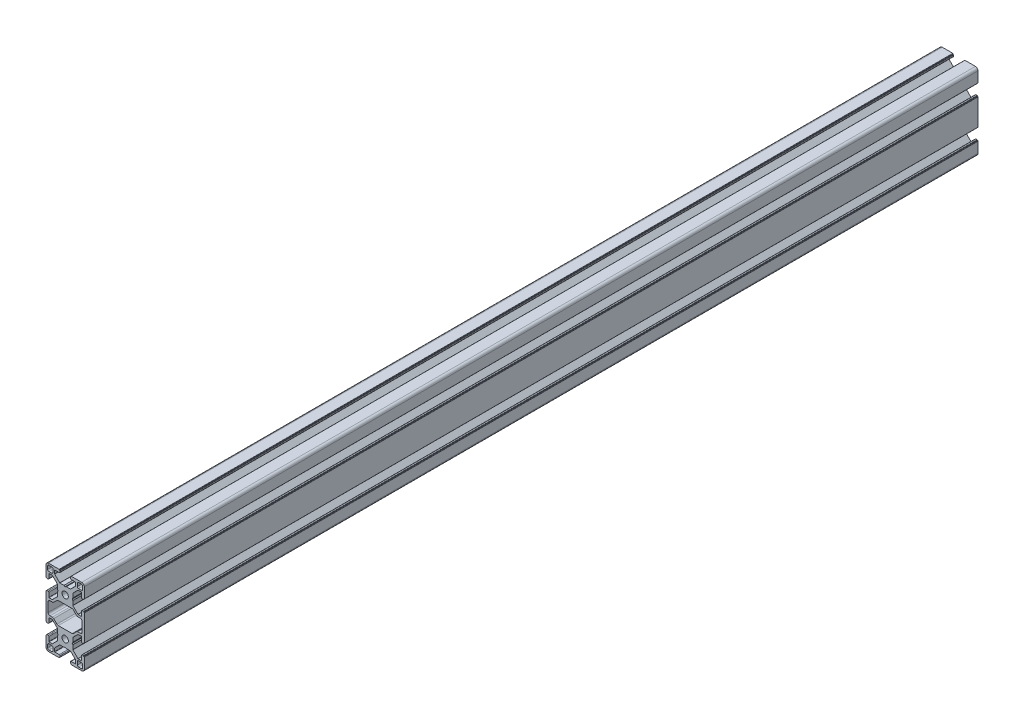
SolidWorks part; units mm, degrees
material "1060 Alloy"
ref_plane "Front" through (0, 0, 0) normal (0, 0, 1) x (1, 0, 0)
ref_plane "Top" through (0, 0, 0) normal (0, 1, 0) x (1, 0, 0)
ref_plane "Right" through (0, 0, 0) normal (1, 0, 0) x (0, 0, -1)
ref_plane "Plane1" through (0, 0, 25) normal (0, 0, 1) x (1, 0, 0)
sketch "Sketch1" plane through (0, 0, 25) normal (0, 0, 1) x (1, 0, 0)
  line L0 (-9.5, 12.7) -> (-9.5, 10.5)
  line L1 (-10.5, 9.5) -> (-12.7, 9.5)
  line L2 (-13.7, 10.5) -> (-13.7, 12.7)
  line L3 (-12.7, 13.7) -> (-10.5, 13.7)
  line L4 (12.7, 9.5) -> (10.5, 9.5)
  line L5 (9.5, 10.5) -> (9.5, 12.7)
  line L6 (10.5, 13.7) -> (12.7, 13.7)
  line L7 (13.7, 12.7) -> (13.7, 10.5)
  line L8 (-12.7, -39.5) -> (-10.5, -39.5)
  line L9 (-9.5, -40.5) -> (-9.5, -42.7)
  line L10 (-10.5, -43.7) -> (-12.7, -43.7)
  line L11 (-13.7, -42.7) -> (-13.7, -40.5)
  line L12 (9.5, -42.7) -> (9.5, -40.5)
  line L13 (10.5, -39.5) -> (12.7, -39.5)
  line L14 (13.7, -40.5) -> (13.7, -42.7)
  line L15 (12.7, -43.7) -> (10.5, -43.7)
  line L16 (0, 0) -> (0, -30) construction
  line L32 (8.9272, -20.5393) -> (6.4104, -23.0562)
  line L33 (5.3497, -23.4955) -> (-5.3497, -23.4955)
  line L34 (-6.4104, -23.0562) -> (-8.9272, -20.5393)
  line L35 (-9.9879, -20.1) -> (-11.85, -20.1)
  line L36 (-13.35, -18.6) -> (-13.35, -11.4)
  line L37 (-11.85, -9.9) -> (-9.9879, -9.9)
  line L38 (-8.9272, -9.4607) -> (-6.4104, -6.9438)
  line L39 (-5.3497, -6.5045) -> (5.3497, -6.5045)
  line L40 (6.4104, -6.9438) -> (8.9272, -9.4607)
  line L41 (9.9879, -9.9) -> (11.85, -9.9)
  line L42 (13.35, -11.4) -> (13.35, -18.6)
  line L43 (11.85, -20.1) -> (9.9879, -20.1)
  line L44 (13.4, -25.95) -> (14.3, -25.95)
  line L45 (14.5, -25.75) -> (14.5, -25.65)
  line L46 (14.7, -25.45) -> (14.8, -25.45)
  line L47 (15, -25.25) -> (15, -4.75)
  line L48 (14.8, -4.55) -> (14.7, -4.55)
  line L49 (14.5, -4.35) -> (14.5, -4.25)
  line L50 (14.3, -4.05) -> (13.4, -4.05)
  line L51 (12.8, -4.65) -> (12.8, -8.05)
  line L52 (12.6, -8.25) -> (10.1328, -8.25)
  line L53 (9.9914, -8.1914) -> (6.063, -4.263)
  line L54 (6.0045, -4.1216) -> (6.0045, -0.9)
  line L55 (6.0045, -0.9) -> (5.5426, -0.1)
  line L56 (5.5426, 0.1) -> (6.0045, 0.9)
  line L57 (6.0045, 0.9) -> (6.0045, 4.1216)
  line L58 (6.063, 4.263) -> (9.9914, 8.1914)
  line L59 (10.1328, 8.25) -> (12.6, 8.25)
  line L60 (12.8, 8.05) -> (12.8, 4.65)
  line L61 (13.4, 4.05) -> (14.3, 4.05)
  line L62 (14.5, 4.25) -> (14.5, 4.35)
  line L63 (14.7, 4.55) -> (14.8, 4.55)
  line L64 (15, 4.75) -> (15, 13)
  line L65 (13, 15) -> (4.75, 15)
  line L66 (4.55, 14.8) -> (4.55, 14.7)
  line L67 (4.35, 14.5) -> (4.25, 14.5)
  line L68 (4.05, 14.3) -> (4.05, 13.4)
  line L69 (4.65, 12.8) -> (8.05, 12.8)
  line L70 (8.25, 12.6) -> (8.25, 10.1328)
  line L71 (8.1914, 9.9914) -> (4.2586, 6.0586)
  line L72 (4.1172, 6) -> (0.9, 6)
  line L73 (0.9, 6) -> (0.1019, 5.5392)
  line L74 (-0.1019, 5.5392) -> (-0.9, 6)
  line L75 (-0.9, 6) -> (-4.1172, 6)
  line L76 (-4.2586, 6.0586) -> (-8.1914, 9.9914)
  line L77 (-8.25, 10.1328) -> (-8.25, 12.6)
  line L78 (-8.05, 12.8) -> (-4.65, 12.8)
  line L79 (-4.05, 13.4) -> (-4.05, 14.3)
  line L80 (-4.25, 14.5) -> (-4.35, 14.5)
  line L81 (-4.55, 14.7) -> (-4.55, 14.8)
  line L82 (-4.75, 15) -> (-13, 15)
  line L83 (-15, 13) -> (-15, 4.75)
  line L84 (-14.8, 4.55) -> (-14.7, 4.55)
  line L85 (-14.5, 4.35) -> (-14.5, 4.25)
  line L86 (-14.3, 4.05) -> (-13.4, 4.05)
  line L87 (-12.8, 4.65) -> (-12.8, 8.05)
  line L88 (-12.6, 8.25) -> (-10.1328, 8.25)
  line L89 (-9.9914, 8.1914) -> (-6.063, 4.263)
  line L90 (-6.0045, 4.1216) -> (-6.0045, 0.9)
  line L91 (-6.0045, 0.9) -> (-5.5426, 0.1)
  line L92 (-5.5426, -0.1) -> (-6.0045, -0.9)
  line L93 (-6.0045, -0.9) -> (-6.0045, -4.1216)
  line L94 (-6.063, -4.263) -> (-9.9914, -8.1914)
  line L95 (-10.1328, -8.25) -> (-12.6, -8.25)
  line L96 (-12.8, -8.05) -> (-12.8, -4.65)
  line L97 (-13.4, -4.05) -> (-14.3, -4.05)
  line L98 (-14.5, -4.25) -> (-14.5, -4.35)
  line L99 (-14.7, -4.55) -> (-14.8, -4.55)
  line L100 (-15, -4.75) -> (-15, -25.25)
  line L101 (-14.8, -25.45) -> (-14.7, -25.45)
  line L102 (-14.5, -25.65) -> (-14.5, -25.75)
  line L103 (-14.3, -25.95) -> (-13.4, -25.95)
  line L104 (-12.8, -25.35) -> (-12.8, -21.95)
  line L105 (-12.6, -21.75) -> (-10.1328, -21.75)
  line L106 (-9.9914, -21.8086) -> (-6.063, -25.737)
  line L107 (-6.0045, -25.8784) -> (-6.0045, -29.1)
  line L108 (-6.0045, -29.1) -> (-5.5426, -29.9)
  line L109 (-5.5426, -30.1) -> (-6.0045, -30.9)
  line L110 (-6.0045, -30.9) -> (-6.0045, -34.1216)
  line L111 (-6.063, -34.263) -> (-9.9914, -38.1914)
  line L112 (-10.1328, -38.25) -> (-12.6, -38.25)
  line L113 (-12.8, -38.05) -> (-12.8, -34.65)
  line L114 (-13.4, -34.05) -> (-14.3, -34.05)
  line L115 (-14.5, -34.25) -> (-14.5, -34.35)
  line L116 (-14.7, -34.55) -> (-14.8, -34.55)
  line L117 (-15, -34.75) -> (-15, -43)
  line L118 (-13, -45) -> (-4.75, -45)
  line L119 (-4.55, -44.8) -> (-4.55, -44.7)
  line L120 (-4.35, -44.5) -> (-4.25, -44.5)
  line L121 (-4.05, -44.3) -> (-4.05, -43.4)
  line L122 (-4.65, -42.8) -> (-8.05, -42.8)
  line L123 (-8.25, -42.6) -> (-8.25, -40.1328)
  line L124 (-8.1914, -39.9914) -> (-4.2586, -36.0586)
  line L125 (-4.1172, -36) -> (-0.9, -36)
  line L126 (-0.9, -36) -> (-0.1019, -35.5392)
  line L127 (0.1019, -35.5392) -> (0.9, -36)
  line L128 (0.9, -36) -> (4.1172, -36)
  line L129 (4.2586, -36.0586) -> (8.1914, -39.9914)
  line L130 (8.25, -40.1328) -> (8.25, -42.6)
  line L131 (8.05, -42.8) -> (4.65, -42.8)
  line L132 (4.05, -43.4) -> (4.05, -44.3)
  line L133 (4.25, -44.5) -> (4.35, -44.5)
  line L134 (4.55, -44.7) -> (4.55, -44.8)
  line L135 (4.75, -45) -> (13, -45)
  line L136 (15, -43) -> (15, -34.75)
  line L137 (14.8, -34.55) -> (14.7, -34.55)
  line L138 (14.5, -34.35) -> (14.5, -34.25)
  line L139 (14.3, -34.05) -> (13.4, -34.05)
  line L140 (12.8, -34.65) -> (12.8, -38.05)
  line L141 (12.6, -38.25) -> (10.1328, -38.25)
  line L142 (9.9914, -38.1914) -> (6.063, -34.263)
  line L143 (6.0045, -34.1216) -> (6.0045, -30.9)
  line L144 (6.0045, -30.9) -> (5.5426, -30.1)
  line L145 (5.5426, -29.9) -> (6.0045, -29.1)
  line L146 (6.0045, -29.1) -> (6.0045, -25.8784)
  line L147 (6.063, -25.737) -> (9.9914, -21.8086)
  line L148 (10.1328, -21.75) -> (12.6, -21.75)
  line L149 (12.8, -21.95) -> (12.8, -25.35)
  arc A0 (-9.5, 10.5) -> (-10.5, 9.5) centre (-10.5, 10.5) cw
  arc A1 (-12.7, 9.5) -> (-13.7, 10.5) centre (-12.7, 10.5) cw
  arc A2 (-13.7, 12.7) -> (-12.7, 13.7) centre (-12.7, 12.7) cw
  arc A3 (-10.5, 13.7) -> (-9.5, 12.7) centre (-10.5, 12.7) cw
  arc A4 (10.5, 9.5) -> (9.5, 10.5) centre (10.5, 10.5) cw
  arc A5 (9.5, 12.7) -> (10.5, 13.7) centre (10.5, 12.7) cw
  arc A6 (12.7, 13.7) -> (13.7, 12.7) centre (12.7, 12.7) cw
  arc A7 (13.7, 10.5) -> (12.7, 9.5) centre (12.7, 10.5) cw
  arc A8 (-10.5, -39.5) -> (-9.5, -40.5) centre (-10.5, -40.5) cw
  arc A9 (-9.5, -42.7) -> (-10.5, -43.7) centre (-10.5, -42.7) cw
  arc A10 (-12.7, -43.7) -> (-13.7, -42.7) centre (-12.7, -42.7) cw
  arc A11 (-13.7, -40.5) -> (-12.7, -39.5) centre (-12.7, -40.5) cw
  arc A12 (9.5, -40.5) -> (10.5, -39.5) centre (10.5, -40.5) cw
  arc A13 (12.7, -39.5) -> (13.7, -40.5) centre (12.7, -40.5) cw
  arc A14 (13.7, -42.7) -> (12.7, -43.7) centre (12.7, -42.7) cw
  arc A15 (10.5, -43.7) -> (9.5, -42.7) centre (10.5, -42.7) cw
  circle A16 centre (0, 0) radius 2.45
  circle A17 centre (0, -30) radius 2.45
  arc A32 (6.4104, -23.0562) -> (5.3497, -23.4955) centre (5.3497, -21.9955) cw
  arc A33 (-5.3497, -23.4955) -> (-6.4104, -23.0562) centre (-5.3497, -21.9955) cw
  arc A34 (-8.9272, -20.5393) -> (-9.9879, -20.1) centre (-9.9879, -21.6) ccw
  arc A35 (-11.85, -20.1) -> (-13.35, -18.6) centre (-11.85, -18.6) cw
  arc A36 (-13.35, -11.4) -> (-11.85, -9.9) centre (-11.85, -11.4) cw
  arc A37 (-9.9879, -9.9) -> (-8.9272, -9.4607) centre (-9.9879, -8.4) ccw
  arc A38 (-6.4104, -6.9438) -> (-5.3497, -6.5045) centre (-5.3497, -8.0045) cw
  arc A39 (5.3497, -6.5045) -> (6.4104, -6.9438) centre (5.3497, -8.0045) cw
  arc A40 (8.9272, -9.4607) -> (9.9879, -9.9) centre (9.9879, -8.4) ccw
  arc A41 (11.85, -9.9) -> (13.35, -11.4) centre (11.85, -11.4) cw
  arc A42 (13.35, -18.6) -> (11.85, -20.1) centre (11.85, -18.6) cw
  arc A43 (9.9879, -20.1) -> (8.9272, -20.5393) centre (9.9879, -21.6) ccw
  arc A44 (12.8, -25.35) -> (13.4, -25.95) centre (13.4, -25.35) ccw
  arc A45 (14.3, -25.95) -> (14.5, -25.75) centre (14.3, -25.75) ccw
  arc A46 (14.5, -25.65) -> (14.7, -25.45) centre (14.7, -25.65) cw
  arc A47 (14.8, -25.45) -> (15, -25.25) centre (14.8, -25.25) ccw
  arc A48 (15, -4.75) -> (14.8, -4.55) centre (14.8, -4.75) ccw
  arc A49 (14.7, -4.55) -> (14.5, -4.35) centre (14.7, -4.35) cw
  arc A50 (14.5, -4.25) -> (14.3, -4.05) centre (14.3, -4.25) ccw
  arc A51 (13.4, -4.05) -> (12.8, -4.65) centre (13.4, -4.65) ccw
  arc A52 (12.8, -8.05) -> (12.6, -8.25) centre (12.6, -8.05) cw
  arc A53 (10.1328, -8.25) -> (9.9914, -8.1914) centre (10.1328, -8.05) cw
  arc A54 (6.063, -4.263) -> (6.0045, -4.1216) centre (6.2045, -4.1216) cw
  arc A55 (5.5426, -0.1) -> (5.5426, 0.1) centre (5.7158, 0) cw
  arc A56 (6.0045, 4.1216) -> (6.063, 4.263) centre (6.2045, 4.1216) cw
  arc A57 (9.9914, 8.1914) -> (10.1328, 8.25) centre (10.1328, 8.05) cw
  arc A58 (12.6, 8.25) -> (12.8, 8.05) centre (12.6, 8.05) cw
  arc A59 (12.8, 4.65) -> (13.4, 4.05) centre (13.4, 4.65) ccw
  arc A60 (14.3, 4.05) -> (14.5, 4.25) centre (14.3, 4.25) ccw
  arc A61 (14.5, 4.35) -> (14.7, 4.55) centre (14.7, 4.35) cw
  arc A62 (14.8, 4.55) -> (15, 4.75) centre (14.8, 4.75) ccw
  arc A63 (15, 13) -> (13, 15) centre (13, 13) ccw
  arc A64 (4.75, 15) -> (4.55, 14.8) centre (4.75, 14.8) ccw
  arc A65 (4.55, 14.7) -> (4.35, 14.5) centre (4.35, 14.7) cw
  arc A66 (4.25, 14.5) -> (4.05, 14.3) centre (4.25, 14.3) ccw
  arc A67 (4.05, 13.4) -> (4.65, 12.8) centre (4.65, 13.4) ccw
  arc A68 (8.05, 12.8) -> (8.25, 12.6) centre (8.05, 12.6) cw
  arc A69 (8.25, 10.1328) -> (8.1914, 9.9914) centre (8.05, 10.1328) cw
  arc A70 (4.2586, 6.0586) -> (4.1172, 6) centre (4.1172, 6.2) cw
  arc A71 (0.1019, 5.5392) -> (-0.1019, 5.5392) centre (0, 5.7158) cw
  arc A72 (-4.1172, 6) -> (-4.2586, 6.0586) centre (-4.1172, 6.2) cw
  arc A73 (-8.1914, 9.9914) -> (-8.25, 10.1328) centre (-8.05, 10.1328) cw
  arc A74 (-8.25, 12.6) -> (-8.05, 12.8) centre (-8.05, 12.6) cw
  arc A75 (-4.65, 12.8) -> (-4.05, 13.4) centre (-4.65, 13.4) ccw
  arc A76 (-4.05, 14.3) -> (-4.25, 14.5) centre (-4.25, 14.3) ccw
  arc A77 (-4.35, 14.5) -> (-4.55, 14.7) centre (-4.35, 14.7) cw
  arc A78 (-4.55, 14.8) -> (-4.75, 15) centre (-4.75, 14.8) ccw
  arc A79 (-13, 15) -> (-15, 13) centre (-13, 13) ccw
  arc A80 (-15, 4.75) -> (-14.8, 4.55) centre (-14.8, 4.75) ccw
  arc A81 (-14.7, 4.55) -> (-14.5, 4.35) centre (-14.7, 4.35) cw
  arc A82 (-14.5, 4.25) -> (-14.3, 4.05) centre (-14.3, 4.25) ccw
  arc A83 (-13.4, 4.05) -> (-12.8, 4.65) centre (-13.4, 4.65) ccw
  arc A84 (-12.8, 8.05) -> (-12.6, 8.25) centre (-12.6, 8.05) cw
  arc A85 (-10.1328, 8.25) -> (-9.9914, 8.1914) centre (-10.1328, 8.05) cw
  arc A86 (-6.063, 4.263) -> (-6.0045, 4.1216) centre (-6.2045, 4.1216) cw
  arc A87 (-5.5426, 0.1) -> (-5.5426, -0.1) centre (-5.7158, 0) cw
  arc A88 (-6.0045, -4.1216) -> (-6.063, -4.263) centre (-6.2045, -4.1216) cw
  arc A89 (-9.9914, -8.1914) -> (-10.1328, -8.25) centre (-10.1328, -8.05) cw
  arc A90 (-12.6, -8.25) -> (-12.8, -8.05) centre (-12.6, -8.05) cw
  arc A91 (-12.8, -4.65) -> (-13.4, -4.05) centre (-13.4, -4.65) ccw
  arc A92 (-14.3, -4.05) -> (-14.5, -4.25) centre (-14.3, -4.25) ccw
  arc A93 (-14.5, -4.35) -> (-14.7, -4.55) centre (-14.7, -4.35) cw
  arc A94 (-14.8, -4.55) -> (-15, -4.75) centre (-14.8, -4.75) ccw
  arc A95 (-15, -25.25) -> (-14.8, -25.45) centre (-14.8, -25.25) ccw
  arc A96 (-14.7, -25.45) -> (-14.5, -25.65) centre (-14.7, -25.65) cw
  arc A97 (-14.5, -25.75) -> (-14.3, -25.95) centre (-14.3, -25.75) ccw
  arc A98 (-13.4, -25.95) -> (-12.8, -25.35) centre (-13.4, -25.35) ccw
  arc A99 (-12.8, -21.95) -> (-12.6, -21.75) centre (-12.6, -21.95) cw
  arc A100 (-10.1328, -21.75) -> (-9.9914, -21.8086) centre (-10.1328, -21.95) cw
  arc A101 (-6.063, -25.737) -> (-6.0045, -25.8784) centre (-6.2045, -25.8784) cw
  arc A102 (-5.5426, -29.9) -> (-5.5426, -30.1) centre (-5.7158, -30) cw
  arc A103 (-6.0045, -34.1216) -> (-6.063, -34.263) centre (-6.2045, -34.1216) cw
  arc A104 (-9.9914, -38.1914) -> (-10.1328, -38.25) centre (-10.1328, -38.05) cw
  arc A105 (-12.6, -38.25) -> (-12.8, -38.05) centre (-12.6, -38.05) cw
  arc A106 (-12.8, -34.65) -> (-13.4, -34.05) centre (-13.4, -34.65) ccw
  arc A107 (-14.3, -34.05) -> (-14.5, -34.25) centre (-14.3, -34.25) ccw
  arc A108 (-14.5, -34.35) -> (-14.7, -34.55) centre (-14.7, -34.35) cw
  arc A109 (-14.8, -34.55) -> (-15, -34.75) centre (-14.8, -34.75) ccw
  arc A110 (-15, -43) -> (-13, -45) centre (-13, -43) ccw
  arc A111 (-4.75, -45) -> (-4.55, -44.8) centre (-4.75, -44.8) ccw
  arc A112 (-4.55, -44.7) -> (-4.35, -44.5) centre (-4.35, -44.7) cw
  arc A113 (-4.25, -44.5) -> (-4.05, -44.3) centre (-4.25, -44.3) ccw
  arc A114 (-4.05, -43.4) -> (-4.65, -42.8) centre (-4.65, -43.4) ccw
  arc A115 (-8.05, -42.8) -> (-8.25, -42.6) centre (-8.05, -42.6) cw
  arc A116 (-8.25, -40.1328) -> (-8.1914, -39.9914) centre (-8.05, -40.1328) cw
  arc A117 (-4.2586, -36.0586) -> (-4.1172, -36) centre (-4.1172, -36.2) cw
  arc A118 (-0.1019, -35.5392) -> (0.1019, -35.5392) centre (0, -35.7158) cw
  arc A119 (4.1172, -36) -> (4.2586, -36.0586) centre (4.1172, -36.2) cw
  arc A120 (8.1914, -39.9914) -> (8.25, -40.1328) centre (8.05, -40.1328) cw
  arc A121 (8.25, -42.6) -> (8.05, -42.8) centre (8.05, -42.6) cw
  arc A122 (4.65, -42.8) -> (4.05, -43.4) centre (4.65, -43.4) ccw
  arc A123 (4.05, -44.3) -> (4.25, -44.5) centre (4.25, -44.3) ccw
  arc A124 (4.35, -44.5) -> (4.55, -44.7) centre (4.35, -44.7) cw
  arc A125 (4.55, -44.8) -> (4.75, -45) centre (4.75, -44.8) ccw
  arc A126 (13, -45) -> (15, -43) centre (13, -43) ccw
  arc A127 (15, -34.75) -> (14.8, -34.55) centre (14.8, -34.75) ccw
  arc A128 (14.7, -34.55) -> (14.5, -34.35) centre (14.7, -34.35) cw
  arc A129 (14.5, -34.25) -> (14.3, -34.05) centre (14.3, -34.25) ccw
  arc A130 (13.4, -34.05) -> (12.8, -34.65) centre (13.4, -34.65) ccw
  arc A131 (12.8, -38.05) -> (12.6, -38.25) centre (12.6, -38.05) cw
  arc A132 (10.1328, -38.25) -> (9.9914, -38.1914) centre (10.1328, -38.05) cw
  arc A133 (6.063, -34.263) -> (6.0045, -34.1216) centre (6.2045, -34.1216) cw
  arc A134 (5.5426, -30.1) -> (5.5426, -29.9) centre (5.7158, -30) cw
  arc A135 (6.0045, -25.8784) -> (6.063, -25.737) centre (6.2045, -25.8784) cw
  arc A136 (9.9914, -21.8086) -> (10.1328, -21.75) centre (10.1328, -21.95) cw
  arc A137 (12.6, -21.75) -> (12.8, -21.95) centre (12.6, -21.95) cw
  dimension "D1" = 4.9
  dimension "D2" = 30
  dimension "D3" = 4.9
extrude "Boss-Extrude1" add sketch "Sketch1" against normal blind 700
sketch "Sketch2" plane through (15, 0, 0) normal (1, 0, 0) x (0, 0, -1)
  line L0 (20, 15) -> (20, -45) construction
  line L1 (675, 15) -> (-25, 15) construction
  line L2 (675, -45) -> (-25, -45) construction
  line L3 (-25, -25.25) -> (-25, -4.75) construction
  line L4 (660, 15) -> (660, -45) construction
  line L5 (675, 4.75) -> (675, 13) construction
  circle A0 centre (20, -30) radius 3
  circle A1 centre (20, 0) radius 3
  circle A2 centre (660, 0) radius 3
  circle A3 centre (660, -30) radius 3
  dimension "D3" = 6
  dimension "D4" = 6
  dimension "D5" = 15
  dimension "D6" = 30
  dimension "D7" = 6
  dimension "D8" = 15
  dimension "D9" = 30
  dimension "D10" = 6
  dimension "D1" = 45
  dimension "D2" = 15
extrude "Cut-Extrude1" cut sketch "Sketch2" against normal through all
sketch "Sketch3" plane through (0, -45, 0) normal (0, -1, 0) x (1, 0, 0)
  line L0 (-15, -20) -> (15, -20) construction
  line L1 (-15, -675) -> (-15, 25) construction
  line L2 (15, -675) -> (15, 25) construction
  line L3 (-15, -660) -> (15, -660) construction
  circle A0 centre (0, -20) radius 3
  circle A1 centre (0, -660) radius 3
  dimension "D2" = 6
  dimension "D4" = 6
  dimension "D1" = 45
  dimension "D3" = 15
extrude "Cut-Extrude2" cut sketch "Sketch3" against normal through all
hole_wizard "M6x1.0 Tapped Hole1" positions "Sketch4" profile "Sketch5" tap size "M6x1.0" standard "ANSI Metric"
sketch "Sketch4" plane through (0, 0, 25) normal (0, 0, 1) x (1, 0, 0)
  point P0 (0, 0)
  point P3 (0, -30)
sketch "Sketch5" plane through (0, 0, 25) normal (1, 0, 0) x (0, -1, 0)
  line L0 (0, 0) -> (0, 29.5022)
  line L1 (0, 29.5022) -> (2.5, 28)
  line L2 (2.5, 28) -> (2.5, 0)
  line L5 (2.5, 0) -> (0, 0)
  line L10 (0, 29.5022) -> (-2.5, 28) construction
  line L11 (0, -6.35) -> (0, 107.95) construction
  dimension "Tap Drill Dia." = 5
  dimension "Tap Drill Depth" = 28
  dimension "Drill Angle" = 118
cosmetic thread "Hole Thread1" parameters "D1"=25, "D2"=6
cosmetic thread "Hole Thread2" parameters "D1"=25, "D2"=6
hole_wizard "M6x1.0 Tapped Hole2" positions "Sketch6" profile "Sketch7" tap size "M6x1.0" standard "ANSI Metric"
sketch "Sketch6" plane through (0, 0, -675) normal (0, 0, -1) x (-1, 0, 0)
  point P0 (0, 0)
  point P3 (0, -30)
sketch "Sketch7" plane through (0, 0, -675) normal (1, 0, 0) x (0, 1, 0)
  line L0 (0, 0) -> (0, 29.5022)
  line L1 (0, 29.5022) -> (2.5, 28)
  line L2 (2.5, 28) -> (2.5, 0)
  line L5 (2.5, 0) -> (0, 0)
  line L10 (0, 29.5022) -> (-2.5, 28) construction
  line L11 (0, -6.35) -> (0, 107.95) construction
  dimension "Tap Drill Dia." = 5
  dimension "Tap Drill Depth" = 28
  dimension "Drill Angle" = 118
cosmetic thread "Hole Thread3" parameters "D1"=25, "D2"=6
cosmetic thread "Hole Thread4" parameters "D1"=25, "D2"=6
